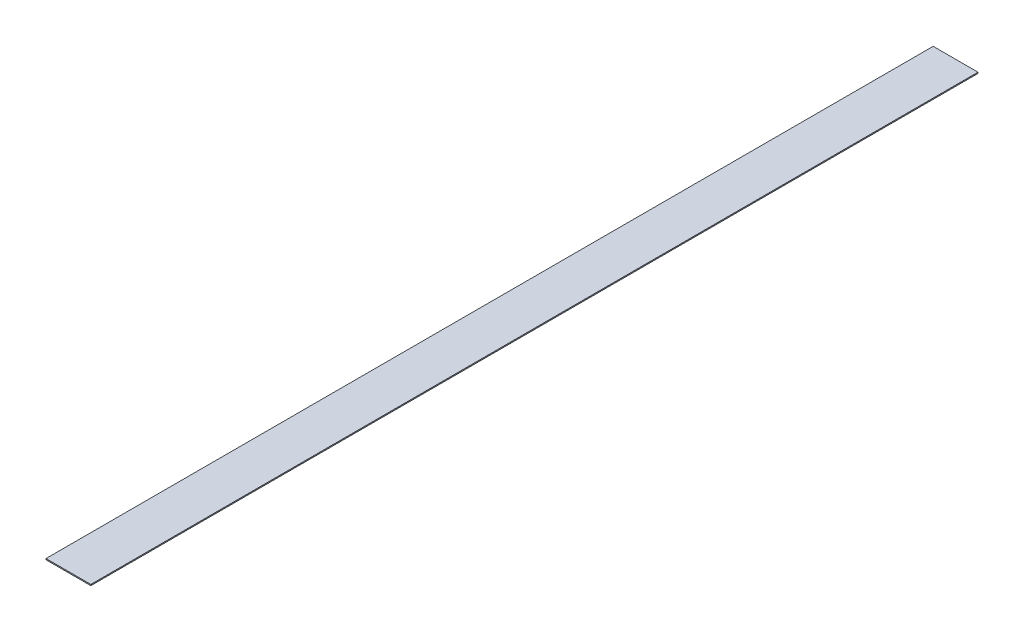
SolidWorks part; units mm, degrees
ref_plane "Front Plane" through (0, 0, 0) normal (0, 0, 1) x (1, 0, 0)
ref_plane "Top Plane" through (0, 0, 0) normal (0, 1, 0) x (1, 0, 0)
ref_plane "Right Plane" through (0, 0, 0) normal (1, 0, 0) x (0, 0, -1)
sketch "Sketch1" plane through (0, 0, 0) normal (0, 1, 0) x (1, 0, 0)
  line L0 (-25.4, 45.466) -> (25.4, 85.6142)
  line L1 (-25.4, -502.666) -> (25.4, -502.666)
  line L2 (-25.4, -502.666) -> (-25.4, 502.666)
  line L3 (-25.4, 502.666) -> (25.4, 502.666)
  line L4 (25.4, -502.666) -> (25.4, 502.666)
  line L5 (-25.4, -502.666) -> (25.4, 502.666) construction
  line L6 (-25.4, 502.666) -> (25.4, -502.666) construction
  point P0 (0, 0)
  dimension "D1" = 50.8
  dimension "D2" = 1005.332
  dimension "D3" = 141.68
  dimension "D4" = 457.2
extrude "Boss-Extrude1" add sketch "Sketch1" along normal blind 1.27 contours L1 L4 L0 L2 | L2 L1 L4 L3 region at (0.2991, 0, 218.4447)
